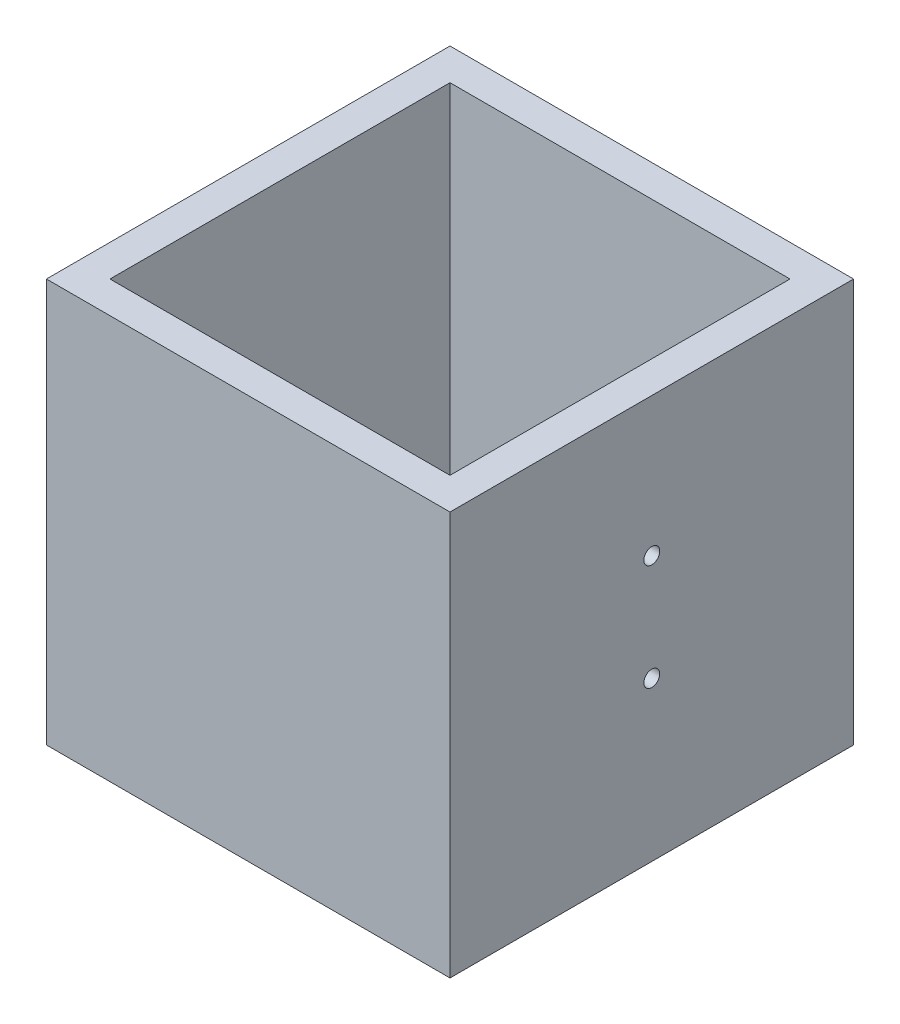
SolidWorks part; units mm, degrees
ref_plane "Front Plane" through (0, 0, 0) normal (0, 0, 1) x (1, 0, 0)
ref_plane "Top Plane" through (0, 0, 0) normal (0, 1, 0) x (1, 0, 0)
ref_plane "Right Plane" through (0, 0, 0) normal (1, 0, 0) x (0, 0, -1)
sketch "Sketch1" plane through (0, 0, 0) normal (0, 1, 0) x (1, 0, 0)
  line L1 (-12.7, -12.7) -> (12.7, -12.7)
  line L2 (-12.7, -12.7) -> (-12.7, 12.7)
  line L3 (-12.7, 12.7) -> (12.7, 12.7)
  line L4 (12.7, -12.7) -> (12.7, 12.7)
  line L5 (-12.7, -12.7) -> (12.7, 12.7) construction
  line L6 (-12.7, 12.7) -> (12.7, -12.7) construction
  point P0 (0, 0)
  dimension "D1" = 25.4
  dimension "D2" = 25.4
extrude "Boss-Extrude1" add sketch "Sketch1" along normal blind 25.4
shell "Shell1" thickness 2 removed face at (0, 25.4, 0)
sketch "Sketch2" plane through (12.7, 0, 0) normal (1, 0, 0) x (0, 0, -1)
  circle A0 centre (0, 9.9849) radius 0.5
  dimension "D1" = 1
extrude "Cut-Extrude1" cut sketch "Sketch2" against normal blind 6.4 contours A0
sketch "Sketch3" plane through (12.7, 0, 0) normal (1, 0, 0) x (0, 0, -1)
  circle A0 centre (0, 16.6696) radius 0.5
  dimension "D1" = 1
extrude "Cut-Extrude2" cut sketch "Sketch3" against normal blind 6.4
shell "Shell2" thickness 1.5 removed face at (-12.7, 12.7, 0)
